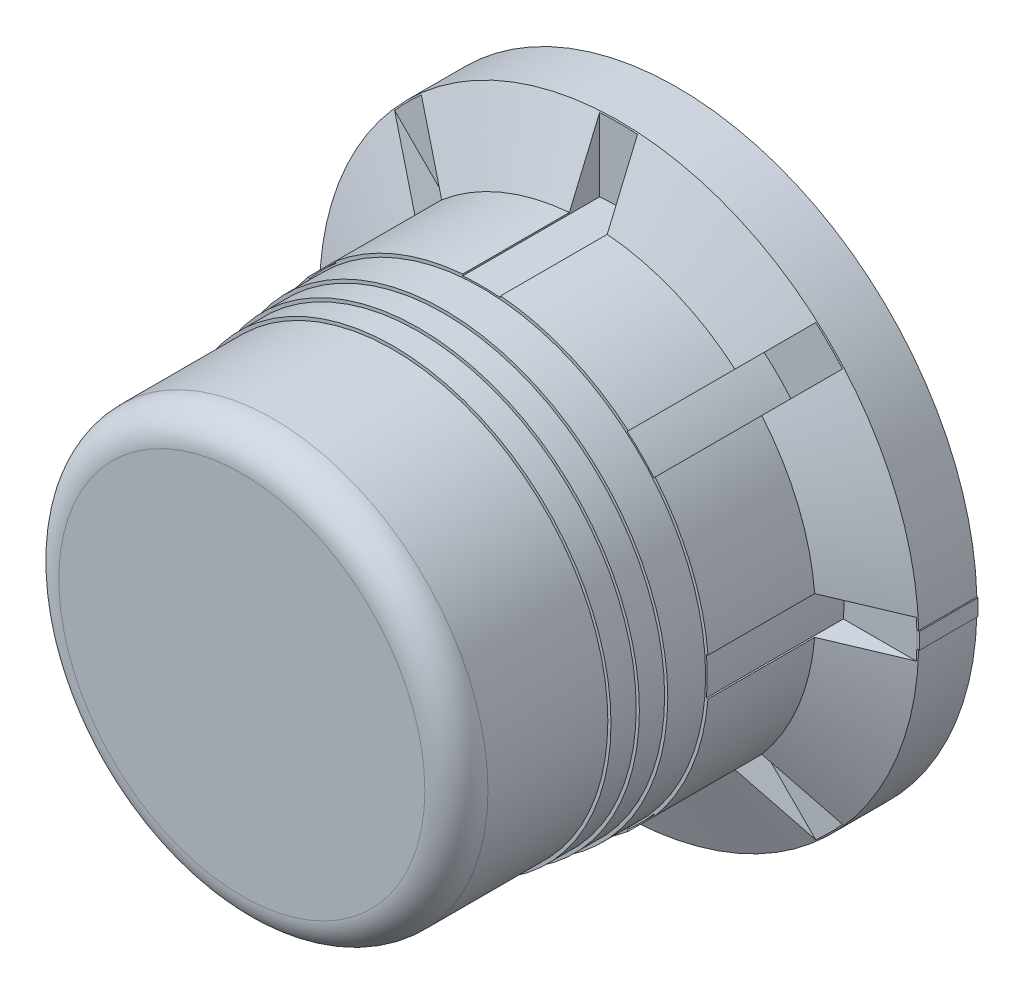
SolidWorks part; units mm, degrees
ref_plane "Alzado" through (0, 0, 0) normal (0, 0, 1) x (1, 0, 0)
ref_plane "Planta" through (0, 0, 0) normal (0, 1, 0) x (1, 0, 0)
ref_plane "Vista lateral" through (0, 0, 0) normal (1, 0, 0) x (0, 0, -1)
sketch "Croquis1" plane through (0, 0, 0) normal (0, 0, 1) x (1, 0, 0)
  circle A0 centre (0, 0) radius 47.5
  dimension "D1" = 95
extrude "Saliente-Extruir1" add sketch "Croquis1" along normal blind 9
sketch "Croquis2" plane through (0, 0, 9) normal (0, 0, 1) x (1, 0, 0)
  circle A0 centre (0, 0) radius 36
  dimension "D1" = 72
extrude "Saliente-Extruir2" add sketch "Croquis2" along normal blind 22
sketch "Croquis3" plane through (0, 0, 31) normal (0, 0, 1) x (1, 0, 0)
  circle A0 centre (0, 0) radius 35.5
  dimension "D1" = 71
extrude "Saliente-Extruir3" add sketch "Croquis3" along normal blind 6
sketch "Croquis4" plane through (0, 0, 37) normal (0, 0, 1) x (1, 0, 0)
  circle A0 centre (0, 0) radius 35
  dimension "D1" = 70
extrude "Saliente-Extruir4" add sketch "Croquis4" along normal blind 4
sketch "Croquis5" plane through (0, 0, 41) normal (0, 0, 1) x (1, 0, 0)
  circle A0 centre (0, 0) radius 34.5
  dimension "D1" = 69
extrude "Saliente-Extruir5" add sketch "Croquis5" along normal blind 4
sketch "Croquis6" plane through (0, 0, 45) normal (0, 0, 1) x (1, 0, 0)
  circle A0 centre (0, 0) radius 34
  dimension "D1" = 68
extrude "Saliente-Extruir6" add sketch "Croquis6" along normal blind 24
fillet "Redondeo1" radius 5 1 edges at (34, 0, 69)
chamfer "Chaflán1" distance 12 angle 23 1 edges at (36, 0, 9) first distance on face at (36, 0, 9)
sketch "Croquis7" plane through (0, 0, 69) normal (0, 0, 1) x (1, 0, 0)
  line L0 (-47.4052, 3) -> (-35.624, 3)
  line L1 (-47.4052, -3) -> (-35.624, -3)
  line L2 (-47.5, 0) -> (-35.7501, 0) construction
  arc A0 (-35.624, 3) -> (-35.624, -3) centre (0, 0) ccw
  circle A2 centre (0, 0) radius 47.5 construction
  arc A3 (-47.4052, 3) -> (-47.4052, -3) centre (0, 0) ccw
  dimension "D1" = 71.5003
  dimension "D2" = 3
  dimension "D3" = 3
extrude "Cortar-Extruir1" cut sketch "Croquis7" against normal blind 59.7
pattern_circular "MatrizC1" count 8 every 45 about axis through (0, 0, 9.2122) along (0, 0, -1) of "Cortar-Extruir1"
sketch "Croquis8" plane through (0, 0, 9.3) normal (0, 0, 1) x (1, 0, 0)
  line L1 (47.6642, 1.2894) -> (47.3358, 1.2894)
  line L2 (47.6642, 1.2894) -> (47.6642, -1.2894)
  line L3 (47.6642, -1.2894) -> (47.3358, -1.2894)
  line L4 (47.3358, 1.2894) -> (47.3358, -1.2894)
  line L5 (47.6642, 1.2894) -> (47.3358, -1.2894) construction
  line L6 (47.6642, -1.2894) -> (47.3358, 1.2894) construction
  circle A0 centre (0, 0) radius 47.5 construction
  point P0 (47.5, 0)
extrude "Saliente-Extruir7" add sketch "Croquis8" against normal up to surface (9.3 mm away) up to face at (47.5, 0, 0)
